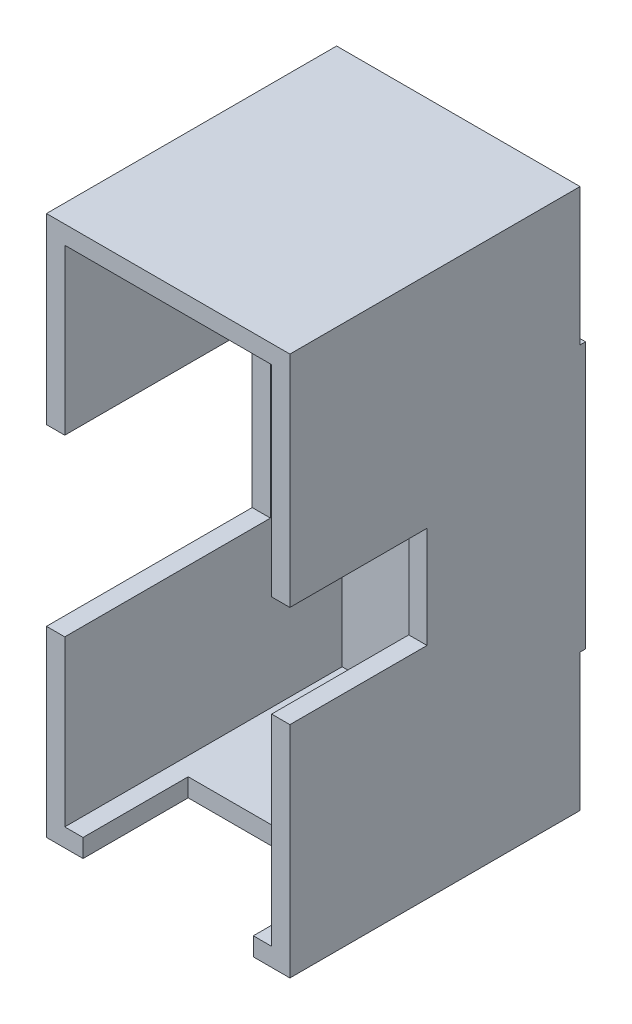
SolidWorks part; units mm, degrees
ref_plane "Front Plane" through (0, 0, 0) normal (0, 0, 1) x (1, 0, 0)
ref_plane "Top Plane" through (0, 0, 0) normal (0, 1, 0) x (1, 0, 0)
ref_plane "Right Plane" through (0, 0, 0) normal (1, 0, 0) x (0, 0, -1)
sketch "Sketch1" plane through (0, 0, 0) normal (0, 0, 1) x (1, 0, 0)
  line L1 (-22.625, -55.1) -> (22.625, -55.1)
  line L2 (-22.625, -55.1) -> (-22.625, 55.1)
  line L3 (-22.625, 55.1) -> (22.625, 55.1)
  line L4 (22.625, -55.1) -> (22.625, 55.1)
  line L5 (-22.625, -55.1) -> (22.625, 55.1) construction
  line L6 (-22.625, 55.1) -> (22.625, -55.1) construction
  line L7 (-26.625, 59.1) -> (26.625, 59.1)
  line L8 (-26.625, 59.1) -> (-26.625, -59.1)
  line L9 (-26.625, -59.1) -> (26.625, -59.1)
  line L10 (26.625, 59.1) -> (26.625, -59.1)
  line L11 (-26.625, 59.1) -> (26.625, -59.1) construction
  line L12 (-26.625, -59.1) -> (26.625, 59.1) construction
  point P0 (0, 0)
  point P6 (0, 0)
  dimension "D1" = 45.25
  dimension "D2" = 110.2
  dimension "D3" = 4
  dimension "D4" = 4
extrude "Boss-Extrude1" add sketch "Sketch1" along normal blind 60.67
sketch "Sketch2" plane through (0, 0, 0) normal (0, 0, 1) x (1, 0, 0)
  line L1 (-26.625, -59.1) -> (26.625, -59.1)
  line L2 (-26.625, -59.1) -> (-26.625, 59.1)
  line L3 (-26.625, 59.1) -> (26.625, 59.1)
  line L4 (26.625, -59.1) -> (26.625, 59.1)
  line L5 (-26.625, -59.1) -> (26.625, 59.1) construction
  line L6 (-26.625, 59.1) -> (26.625, -59.1) construction
  point P0 (0, 0)
extrude "Boss-Extrude2" add sketch "Sketch2" against normal blind 4 contours L2 L1 L4 L3
sketch "Sketch3" plane through (26.625, 0, 0) normal (1, 0, 0) x (0, 0, -1)
  line L0 (-60.67, -59.1) -> (-60.67, 59.1) construction
  line L1 (-60.67, 11.1) -> (-30.67, 11.1)
  line L2 (-60.67, 11.1) -> (-60.67, -11.1)
  line L3 (-60.67, -11.1) -> (-30.67, -11.1)
  line L4 (-30.67, 11.1) -> (-30.67, -11.1)
  line L5 (-60.67, 59.1) -> (4, 59.1) construction
  line L6 (-60.67, -59.1) -> (4, -59.1) construction
  dimension "D1" = 48
  dimension "D2" = 48
  dimension "D3" = 30
extrude "Cut-Extrude1" cut sketch "Sketch3" against normal blind 4
sketch "Sketch4" plane through (-26.625, 0, 0) normal (-1, 0, 0) x (0, 0, 1)
  line L6 (60.67, -59.1) -> (-4, -59.1) construction
  line L8 (28.335, -59.1) -> (28.335, 63.777) construction
  line L9 (60.67, -19.1) -> (15.67, -19.1)
  line L10 (15.67, 19.1) -> (15.67, -19.1)
  line L11 (60.67, 19.1) -> (15.67, 19.1)
  line L12 (60.67, 19.1) -> (60.67, -19.1)
  line L13 (60.67, 59.1) -> (-4, 59.1) construction
  line L14 (60.67, 59.1) -> (60.67, -59.1) construction
  dimension "D1" = 45
  dimension "D2" = 40
  dimension "D3" = 40
extrude "Cut-Extrude2" cut sketch "Sketch4" against normal blind 4
sketch "Sketch5" plane through (0, -59.1, 0) normal (0, -1, 0) x (1, 0, 0)
  line L0 (-26.625, 60.67) -> (26.625, 60.67) construction
  line L1 (-18.625, 60.67) -> (18.625, 60.67)
  line L2 (-18.625, 60.67) -> (-18.625, 37.67)
  line L3 (-18.625, 37.67) -> (18.625, 37.67)
  line L4 (18.625, 60.67) -> (18.625, 37.67)
  line L5 (26.625, 60.67) -> (26.625, -4) construction
  line L6 (-26.625, 60.67) -> (-26.625, -4) construction
  dimension "D1" = 23
  dimension "D2" = 8
  dimension "D3" = 8
extrude "Cut-Extrude3" cut sketch "Sketch5" against normal blind 4
sketch "Sketch6" plane through (0, 0, 0) normal (0, 0, 1) x (1, 0, 0)
  circle A0 centre (0, 0) radius 6
  circle A1 centre (0, 0) radius 8
  dimension "D1" = 12
  dimension "D2" = 16
extrude "Boss-Extrude3" add sketch "Sketch6" along normal blind 1.5
sketch "Sketch8" plane through (0, 0, 1.5) normal (0, 0, 1) x (1, 0, 0)
  circle A0 centre (0, 0) radius 8
  dimension "D1" = 16
sketch "Sketch9" plane through (0, 0, -4) normal (0, 0, -1) x (-1, 0, 0)
  circle A0 centre (0, 0) radius 6
  dimension "D1" = 12
extrude "Cut-Extrude4" cut sketch "Sketch9" against normal blind 5.5
sketch "Sketch10" plane through (26.625, 0, 0) normal (1, 0, 0) x (0, 0, -1)
  line L0 (0, 0) -> (22.7501, 0) construction
  line L1 (4, -59.1) -> (2.8, -59.1)
  line L2 (4, -59.1) -> (4, -29.1)
  line L3 (4, -29.1) -> (2.8, -29.1)
  line L4 (2.8, -59.1) -> (2.8, -29.1)
  line L5 (4, 29.1) -> (2.8, 29.1)
  line L6 (2.8, 59.1) -> (2.8, 29.1)
  line L7 (4, 59.1) -> (2.8, 59.1)
  line L8 (4, 59.1) -> (4, 29.1)
  line M16 (4, -59.1) -> (4, 59.1)
  line M17 (4, 59.1) -> (-60.67, 59.1)
  dimension "D1" = 30
  dimension "D2" = 1.2
extrude "Cut-Extrude6" cut sketch "Sketch10" against normal through all contours L6 L5 M17 M16 | L2 L1 L4 L3 region at (26.625, 44.1, -3.4)
extrude "Boss-Extrude5" add sketch "Sketch8" along normal blind 3
sketch "Sketch12" plane through (0, 0, 4.5) normal (0, 0, 1) x (1, 0, 0)
  circle A0 centre (0, 0) radius 3.325
  dimension "D1" = 6.65
extrude "Cut-Extrude8" cut sketch "Sketch12" against normal through all
